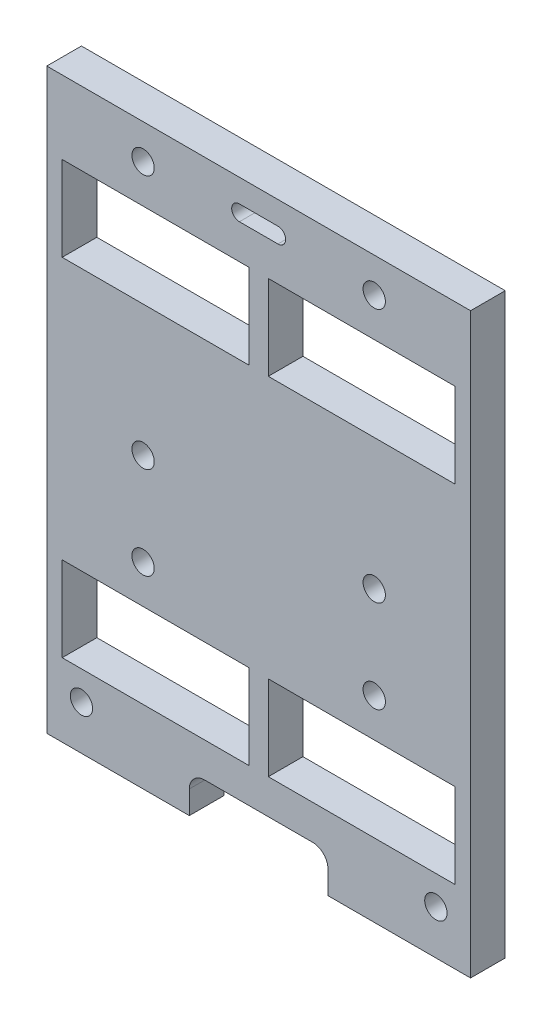
SolidWorks part; units mm, degrees
ref_plane "Front Plane" through (0, 0, 0) normal (0, 0, 1) x (1, 0, 0)
ref_plane "Top Plane" through (0, 0, 0) normal (0, 1, 0) x (1, 0, 0)
ref_plane "Right Plane" through (0, 0, 0) normal (1, 0, 0) x (0, 0, -1)
sketch "Sketch1" plane through (0, 0, 0) normal (0, 0, 1) x (1, 0, 0)
  line L0 (0, -37.5) -> (0, 37.5) construction
  line L1 (-27.5, -37.5) -> (27.5, -37.5)
  line L2 (-27.5, -37.5) -> (-27.5, 37.5)
  line L3 (-27.5, 37.5) -> (27.5, 37.5)
  line L4 (27.5, -37.5) -> (27.5, 37.5)
  line L5 (-27.5, -37.5) -> (27.5, 37.5) construction
  line L6 (-27.5, 37.5) -> (27.5, -37.5) construction
  line L7 (-27.5, 0) -> (27.5, 0) construction
  line L8 (-27.5, 22.5) -> (27.5, 22.5) construction
  line L9 (25.5, 17) -> (1.25, 28) construction
  line L10 (-25.5, 28) -> (-1.25, 28)
  line L11 (-25.5, 28) -> (-25.5, 17)
  line L12 (-25.5, 17) -> (-1.25, 17)
  line L13 (-1.25, 28) -> (-1.25, 17)
  line L14 (-25.5, 28) -> (-1.25, 17) construction
  line L15 (-25.5, 17) -> (-1.25, 28) construction
  line L16 (25.5, 28) -> (1.25, 17) construction
  line L17 (1.25, 28) -> (1.25, 17)
  line L18 (25.5, 17) -> (1.25, 17)
  line L19 (25.5, 28) -> (25.5, 17)
  line L20 (25.5, 28) -> (1.25, 28)
  line L21 (25.5, -28) -> (1.25, -17) construction
  line L22 (-25.5, -17) -> (-1.25, -28) construction
  line L23 (-25.5, -28) -> (-1.25, -17) construction
  line L24 (25.5, -17) -> (1.25, -28) construction
  line L25 (25.5, -28) -> (1.25, -28)
  line L26 (25.5, -28) -> (25.5, -17)
  line L27 (25.5, -17) -> (1.25, -17)
  line L28 (1.25, -28) -> (1.25, -17)
  line L29 (-1.25, -28) -> (-1.25, -17)
  line L30 (-25.5, -17) -> (-1.25, -17)
  line L31 (-25.5, -28) -> (-25.5, -17)
  line L32 (-25.5, -28) -> (-1.25, -28)
  point P0 (0, 0)
  point P12 (-13.375, 22.5)
  point P21 (13.375, 22.5)
  point P30 (13.375, -22.5)
  point P31 (-13.375, -22.5)
  dimension "D1" = 55
  dimension "D2" = 75
  dimension "D3" = 22.5
  dimension "D4" = 24.25
  dimension "D5" = 11
  dimension "D6" = 1.25
extrude "Boss-Extrude1" add sketch "Sketch1" along normal blind 4.5
sketch "Sketch2" plane through (0, 0, 4.5) normal (0, 0, 1) x (1, 0, 0)
  line L0 (0, -37.5) -> (0, 37.5) construction
  line L1 (-27.5, -37.5) -> (27.5, -37.5) construction
  line L2 (27.5, 37.5) -> (-27.5, 37.5) construction
  line L3 (-27.5, 0) -> (27.5, 0) construction
  line L4 (-27.5, 37.5) -> (-27.5, -37.5) construction
  line L5 (27.5, -37.5) -> (27.5, 37.5) construction
  line L6 (-15, 0) -> (15, 0) construction
  circle A0 centre (-15, 33) radius 1.45
  circle A1 centre (15, 33) radius 1.45
  circle A2 centre (15, 0) radius 1.45
  circle A3 centre (-15, 0) radius 1.45
  dimension "D1" = 2.9
  dimension "D7" = 2.9
  dimension "D8" = 2.9
  dimension "D2" = 15
  dimension "D3" = 33
  dimension "D4" = 30
  dimension "D5" = 15
  dimension "D6" = 0
extrude "screwHoles" cut sketch "Sketch2" against normal through all
sketch "Sketch3" plane through (0, 0, 4.5) normal (0, 0, 1) x (1, 0, 0)
  line L0 (-27.5, 9) -> (26.0486, 9) construction
  line L1 (-27.5, 37.5) -> (-27.5, -37.5) construction
  line L3 (0, 37.5) -> (0, -37.5) construction
  line L4 (27.5, 37.5) -> (-27.5, 37.5) construction
  line L5 (-27.5, -37.5) -> (27.5, -37.5) construction
  line L6 (18.95, 6.8) -> (9.05, 11.2) construction
  line L7 (-18.95, 11.2) -> (-9.05, 11.2)
  line L8 (-18.95, 11.2) -> (-18.95, 6.8)
  line L9 (-18.95, 6.8) -> (-9.05, 6.8)
  line L10 (-9.05, 11.2) -> (-9.05, 6.8)
  line L11 (-18.95, 11.2) -> (-9.05, 6.8) construction
  line L12 (-18.95, 6.8) -> (-9.05, 11.2) construction
  line L13 (18.95, 11.2) -> (9.05, 6.8) construction
  line L14 (9.05, 11.2) -> (9.05, 6.8)
  line L15 (18.95, 6.8) -> (9.05, 6.8)
  line L16 (18.95, 11.2) -> (18.95, 6.8)
  line L17 (18.95, 11.2) -> (9.05, 11.2)
  line L18 (-27.5, 37.5) -> (-27.5, -37.5) construction
  point P2 (-27.5, 0)
  point P12 (-14, 9)
  point P21 (14, 9)
  dimension "D1" = 9.9
  dimension "D2" = 4.4
  dimension "D3" = 14
  dimension "D4" = 9
extrude "BeltClamp" [suppressed] cut sketch "Sketch3" against normal through all
sketch "Sketch4" plane through (0, 0, 4.5) normal (0, 0, 1) x (1, 0, 0)
  line L0 (-27.5, 0) -> (27.5, 0) construction
  line L1 (-27.5, 37.5) -> (-27.5, -37.5) construction
  line L2 (27.5, -37.5) -> (27.5, 37.5) construction
  line L4 (-4.9, 2.2) -> (4.9, 2.2)
  line L5 (-4.9, 2.2) -> (-4.9, -2.2)
  line L6 (-4.9, -2.2) -> (4.9, -2.2)
  line L7 (4.9, 2.2) -> (4.9, -2.2)
  line L8 (-4.9, 2.2) -> (4.9, -2.2) construction
  line L9 (-4.9, -2.2) -> (4.9, 2.2) construction
  circle A0 centre (-15, 0) radius 1.45 construction
  point P6 (0, 0)
  dimension "D2" = 4.4
  dimension "D3" = 0
extrude "mountingPlateTab" [suppressed] cut sketch "Sketch4" against normal through all
sketch "Sketch5" plane through (0, 0, 4.5) normal (0, 0, 1) x (1, 0, 0)
  line L0 (-27.5, -9.75) -> (27.5, -9.75) construction
  line L1 (-27.5, 37.5) -> (-27.5, -37.5) construction
  line L2 (27.5, -37.5) -> (27.5, 37.5) construction
  line L4 (0, -37.5) -> (0, 37.5) construction
  line L5 (-27.5, -37.5) -> (27.5, -37.5) construction
  line L6 (27.5, 37.5) -> (-27.5, 37.5) construction
  line L7 (-20.8, -14.65) -> (-25.2, -4.85) construction
  line L8 (20.8, -4.85) -> (25.2, -4.85)
  line L9 (20.8, -4.85) -> (20.8, -14.65)
  line L10 (20.8, -14.65) -> (25.2, -14.65)
  line L11 (25.2, -4.85) -> (25.2, -14.65)
  line L12 (20.8, -4.85) -> (25.2, -14.65) construction
  line L13 (20.8, -14.65) -> (25.2, -4.85) construction
  line L14 (-20.8, -4.85) -> (-25.2, -14.65) construction
  line L15 (-25.2, -4.85) -> (-25.2, -14.65)
  line L16 (-20.8, -14.65) -> (-25.2, -14.65)
  line L17 (-20.8, -4.85) -> (-20.8, -14.65)
  line L18 (-20.8, -4.85) -> (-25.2, -4.85)
  line L19 (23, -9.75) -> (23, -37.5) construction
  line L20 (-23, -9.75) -> (-23, -37.5) construction
  circle A0 centre (23, -31.75) radius 1.45
  circle A1 centre (-23, -31.75) radius 1.45
  point P15 (23, -9.75)
  point P24 (-23, -9.75)
  dimension "D5" = 2.9
  dimension "D2" = 9.8
  dimension "D3" = 4.4
  dimension "D4" = 23
  dimension "D6" = 22
  dimension "D1" = 9.75
extrude "BraceTabs" cut sketch "Sketch5" against normal through all
sketch "Sketch6" [suppressed] plane through (0, 0, 4.5) normal (0, 0, 1) x (1, 0, 0)
  line L0 (-25.2, -9.75) -> (25.2, -9.75) construction
  line L1 (-25.2, -4.85) -> (-25.2, -14.65) construction
  line L2 (25.2, -14.65) -> (25.2, -4.85) construction
  line L3 (0, -2.2) -> (0, -37.5) construction
  line L4 (-4.9, -2.2) -> (4.9, -2.2) construction
  line L5 (-27.5, -37.5) -> (27.5, -37.5) construction
  line L6 (23, -14.65) -> (23, -4.85) construction
  line L7 (20.8, -14.65) -> (25.2, -14.65) construction
  line L8 (25.2, -4.85) -> (20.8, -4.85) construction
  line L9 (20.8, -4.85) -> (20.8, -14.65) construction
  line L10 (19.8, -15.65) -> (26.2, -15.65)
  line L11 (19.8, -15.65) -> (19.8, -3.85)
  line L12 (19.8, -3.85) -> (26.2, -3.85)
  line L13 (26.2, -15.65) -> (26.2, -3.85)
  line L14 (19.8, -15.65) -> (26.2, -3.85) construction
  line L15 (19.8, -3.85) -> (26.2, -15.65) construction
  line L16 (-19.8, -3.85) -> (-26.2, -15.65) construction
  line L17 (-19.8, -15.65) -> (-26.2, -3.85) construction
  line L18 (-23, -14.65) -> (-23, -4.85) construction
  line L19 (-26.2, -15.65) -> (-26.2, -3.85)
  line L20 (-19.8, -3.85) -> (-26.2, -3.85)
  line L21 (-19.8, -15.65) -> (-19.8, -3.85)
  line L22 (-19.8, -15.65) -> (-26.2, -15.65)
  circle A0 centre (23, -9.75) radius 1.45
  circle A1 centre (-23, -9.75) radius 1.45
  point P18 (23, -9.75)
  dimension "D3" = 2.9
  dimension "D1" = 1
  dimension "D2" = 1
extrude "FrontToRear1" [suppressed] add sketch "Sketch6" against normal up to surface (4.5 mm away) up to face at (-24.45, -31.75, 0)
sketch "Sketch7" [suppressed] plane through (0, 0, 4.5) normal (0, 0, 1) x (1, 0, 0)
  line L0 (4.9, 2.2) -> (-4.9, 2.2) construction
  line L1 (-20, -3.2) -> (20, -3.2)
  line L2 (-20, -3.2) -> (-20, 3.2)
  line L3 (-20, 3.2) -> (20, 3.2)
  line L4 (20, -3.2) -> (20, 3.2)
  line L5 (-20, -3.2) -> (20, 3.2) construction
  line L6 (-20, 3.2) -> (20, -3.2) construction
  circle A0 centre (15, 0) radius 1.45 construction
  point P0 (0, 0)
  dimension "D1" = 1
  dimension "D2" = 5
extrude "FrontToRear2" [suppressed] add sketch "Sketch7" against normal through all
sketch "Sketch8" plane through (0, 0, 4.5) normal (0, 0, 1) x (1, 0, 0)
  line L0 (-27.5, -12) -> (27.5, -12) construction
  line L1 (-27.5, 37.5) -> (-27.5, -37.5) construction
  line L2 (27.5, -37.5) -> (27.5, 37.5) construction
  line L3 (0, -37.5) -> (0, 0) construction
  line L4 (-27.5, -37.5) -> (27.5, -37.5) construction
  circle A0 centre (-15, -12) radius 1.45
  circle A1 centre (15, -12) radius 1.45
  dimension "D2" = 2.9
  dimension "D1" = 12
  dimension "D3" = 15
extrude "ExpansionScrewholes" cut sketch "Sketch8" against normal through all
sketch "Sketch12" plane through (0, 0, 4.5) normal (0, 0, 1) x (1, 0, 0)
  line L0 (0, 37.5) -> (0, 0) construction
  line L1 (27.5, 37.5) -> (-27.5, 37.5) construction
  line L2 (-2.5, 33.5) -> (2.5, 33.5) construction
  line L3 (-2.5, 34.5) -> (2.5, 34.5)
  line L4 (-2.5, 32.5) -> (2.5, 32.5)
  arc A0 (-2.5, 34.5) -> (-2.5, 32.5) centre (-2.5, 33.5) ccw
  arc A1 (2.5, 32.5) -> (2.5, 34.5) centre (2.5, 33.5) ccw
  point P7 (0, 33.5)
  dimension "D1" = 3
  dimension "D2" = 2
  dimension "D3" = 5
extrude "CableTieSlot" cut sketch "Sketch12" against normal through all
sketch "Sketch11" plane through (0, 0, 4.5) normal (0, 0, 1) x (1, 0, 0)
  line L0 (13.5615, -8.65) -> (27.5, -8.65) construction
  line L1 (27.5, -37.5) -> (27.5, 37.5) construction
  line L2 (0, 37.5) -> (0, -37.5) construction
  line L3 (36.5, -14.65) -> (18.5, -14.65)
  line L4 (36.5, -14.65) -> (36.5, -2.65)
  line L5 (36.5, -2.65) -> (18.5, -2.65)
  line L6 (18.5, -14.65) -> (18.5, -2.65)
  line L7 (36.5, -14.65) -> (18.5, -2.65) construction
  line L8 (36.5, -2.65) -> (18.5, -14.65) construction
  line L11 (-36.5, -2.65) -> (-18.5, -14.65) construction
  line L12 (-36.5, -14.65) -> (-18.5, -2.65) construction
  line L13 (-18.5, -14.65) -> (-18.5, -2.65)
  line L14 (-36.5, -2.65) -> (-18.5, -2.65)
  line L15 (-36.5, -14.65) -> (-36.5, -2.65)
  line L16 (-36.5, -14.65) -> (-18.5, -14.65)
  line L17 (36.5, -2.65) -> (18.5, -14.65) construction
  line L18 (20.8, -14.65) -> (25.2, -14.65) construction
  line L19 (27.5, 37.5) -> (-27.5, 37.5) construction
  line L20 (-27.5, -37.5) -> (27.5, -37.5) construction
  dimension "D1" = 9
  dimension "D2" = 12
  dimension "D3" = 0
extrude "Cut-Extrude2" [suppressed] cut sketch "Sketch11" against normal through all
sketch "Sketch10" [suppressed] plane through (0, 0, 4.5) normal (0, 0, 1) x (1, 0, 0)
  line L0 (4.7446, 1) -> (27.5, 1) construction
  line L1 (-4.9, 0) -> (4.9, 0) construction
  line L2 (27.5, -37.5) -> (27.5, 37.5) construction
  line L3 (0, 2.2) -> (0, -2.2) construction
  line L4 (36.5, 4) -> (18.5, 4)
  line L5 (36.5, 4) -> (36.5, -2)
  line L6 (36.5, -2) -> (18.5, -2)
  line L7 (18.5, 4) -> (18.5, -2)
  line L8 (36.5, 4) -> (18.5, -2) construction
  line L9 (36.5, -2) -> (18.5, 4) construction
  line L10 (4.9, 2.2) -> (-4.9, 2.2) construction
  line L11 (-4.9, -2.2) -> (4.9, -2.2) construction
  line L12 (-36.5, -2) -> (-18.5, 4) construction
  line L13 (-36.5, 4) -> (-18.5, -2) construction
  line L14 (-4.7446, 1) -> (-27.5, 1) construction
  line L15 (-18.5, 4) -> (-18.5, -2)
  line L16 (-36.5, -2) -> (-18.5, -2)
  line L17 (-36.5, 4) -> (-36.5, -2)
  line L18 (-36.5, 4) -> (-18.5, 4)
  line L19 (36.5, -2) -> (18.5, 4) construction
  line L20 (-4.9, 2.2) -> (-4.9, -2.2) construction
  line L21 (4.9, -2.2) -> (4.9, 2.2) construction
  dimension "D1" = 6
  dimension "D2" = 9
  dimension "D3" = 1
extrude "CableTieSlots" [suppressed] cut sketch "Sketch10" against normal through all
sketch "Sketch9" plane through (0, 0, 4.5) normal (0, 0, 1) x (1, 0, 0)
  line L0 (-27.5, -37.5) -> (27.5, -37.5) construction
  line L5 (-9, -42.5) -> (9, -42.5)
  line L6 (-9, -42.5) -> (-9, -34.5)
  line L7 (-7, -32.5) -> (7, -32.5)
  line L8 (9, -42.5) -> (9, -34.5)
  line L9 (-9, -42.5) -> (9, -32.5) construction
  line L10 (-9, -32.5) -> (9, -42.5) construction
  arc A0 (7, -32.5) -> (9, -34.5) centre (7, -34.5) cw
  arc A1 (-9, -34.5) -> (-7, -32.5) centre (-7, -34.5) cw
  point P9 (0, -37.5)
  line M42 (-27.5, -37.5) -> (27.5, -37.5)
  dimension "D3" = 2
  dimension "D1" = 18
  dimension "D2" = 5
extrude "RearFanSlot" cut sketch "Sketch9" against normal through all contours A1 L6 L8 A0 L7 M42 | L5 L8 L6 M42
sketch "Sketch13" [suppressed] plane through (0, 0, 4.5) normal (0, 0, 1) x (1, 0, 0)
  line L1 (-7, -2.85) -> (7, -2.85)
  line L2 (-7, -2.85) -> (-7, -11.85)
  line L3 (-7, -11.85) -> (7, -11.85)
  line L4 (7, -2.85) -> (7, -11.85)
  line L5 (-7, -2.85) -> (7, -11.85) construction
  line L6 (-7, -11.85) -> (7, -2.85) construction
  line L9 (0, 37.5) -> (0, -7.35) construction
  line L10 (-18.5, -2.85) -> (-27.5, -2.85) construction
  line L11 (27.5, 37.5) -> (-27.5, 37.5) construction
  line L13 (-27.5, -14.85) -> (-18.5, -14.85) construction
  point P0 (0, -7.35)
  dimension "D1" = 3
  dimension "D2" = 0
  dimension "D3" = 7
extrude "Cut-Extrude3" [suppressed] cut sketch "Sketch13" against normal through all
sketch "Sketch14" plane through (0, 0, 4.5) normal (0, 0, 1) x (1, 0, 0)
  line L0 (25.2, -4.85) -> (20.8, -4.85) construction
  line L1 (25.2, -4.85) -> (20.8, -4.85)
  line L2 (25.2, -4.85) -> (25.2, -14.65)
  line L3 (25.2, -14.65) -> (20.8, -14.65)
  line L4 (20.8, -4.85) -> (20.8, -14.65)
  line L5 (25.2, -14.65) -> (25.2, -4.85) construction
  line L6 (0, 0) -> (0, -6.835) construction
  line L7 (-20.8, -4.85) -> (-20.8, -14.65)
  line L8 (-25.2, -14.65) -> (-20.8, -14.65)
  line L9 (-25.2, -4.85) -> (-25.2, -14.65)
  line L10 (-25.2, -4.85) -> (-20.8, -4.85)
extrude "Boss-Extrude2" add sketch "Sketch14" against normal through all
equation "\"X-ROD-SPACING\"=45"
equation "\"Y-ROD-SPACING\"=75"
equation "\"Z-ROD-SPACING\"=17.5"
equation "\"Y-BED-OFFSET\"=2"
equation "\"Y-BED-ROD-INSET\"=3.5"
equation "\"Y-BED-SCREW-SPACING\"=209"
equation "\"Y-BED-SCREW-CUTOUT-SLOT-HEIGHT\"=2"
equation "\"T-SLOT-NUT-FILLET-RADIUS\"=0.5"
equation "\"T-SLOT-SCREW-SHAFT-RADIUS\"=1.55"
equation "\"T-SLOT-SCREW-SHAFT-CUTOUT-LENGTH\"=11.0"
equation "\"T-SLOT-NUT-DEPTH\"=3.5"
equation "\"T-SLOT-NUT-WIDTH\"=2.85"
equation "\"T-SLOT-NUT-END-DISTANCE\"=8"
equation "\"ACRYLIC-THICKNESS\"=10"
equation "\"ACRYLIC-THICKNESS2\"=4.5"
equation "\"ACRYLIC-TAB-CUTOUT-SIZE\"=\"ACRYLIC-THICKNESS\"+\"ACRYLIC-TAB-TOLERANCE\"*2"
equation "\"ACRYLIC-TAB-WIDTH\"=\"ACRYLIC-THICKNESS\""
equation "\"ACRYLIC-M3-HOLE\"=2.9"
equation "\"SMOOTHROD-CAP-SCREW-DISTANCE\"=20"
equation "\"FRAME-WIDTH-INNER\"=370"
equation "\"NEMA17-HOLE-SPACING\"=31"
equation "\"NEMA17-CENTRAL-CUTOUT\"=22.5"
equation "\"Z-BRACKET-REACH\"=55"
equation "\"Z-ROD-INSET\"=16"
equation "\"TOP-BRACKET-SPACING\"=40"
equation "\"SMOOTHROD-X-LENGTH\"=350"
equation "\"SMOOTHROD-Y-LENGTH\"=350"
equation "\"SMOOTHROD-Z-LENGTH\"=350"
equation "\"SMOOTHROD-TIGHTENING-HEADROOM\"=.25"
equation "\"LEADSCREW-Z-LENGTH\"=300"
equation "\"SCREW-LENGTH-FRAME\"=\"ACRYLIC-THICKNESS\" + 10"
equation "\"SCREW-LENGTH-MOTOR\"=\"ACRYLIC-THICKNESS\" + 5"
equation "\"SCREW-HEAD-RADIUS\"=6"
equation "\"PRINTED-X-SMOOTHROD-DIAMETER\"=8.4"
equation "\"PRINTED-X-SMOOTHROD-CUTOUT\"=10"
equation "\"PRINTED-X-BASE-HEIGHT\"=10"
equation "\"PRINTED-LM8UU-CUTOUT-SIZE\"=15.5"
equation "\"PRINTED-LM8UU-CUTOUT-LENGTH\"=24.5"
equation "\"PRINTED-X-IDLER-HEIGHT\"=16"
equation "\"PSU-MOUNTING-WIDTH\"=95"
equation "\"PSU-MOUNTING-HEIGHT\"=177"
equation "\"Y-BELT-TO-ROD-DISTANCE\"=20"
equation "\"SPOOL-HOLDER-ROD-SPACING\"=150"
equation "\"D3@Sketch1\"=\"X-ROD-SPACING\"/2"
equation "\"D4@Sketch1\"=\"ACRYLIC-X-CARRIAGE-LM8UU-CUTOUT-WIDTH\""
equation "\"D1@Boss-Extrude1\"=\"ACRYLIC-THICKNESS2\""
equation "\"D1@Sketch2\"=\"ACRYLIC-M3-HOLE\""
equation "\"D1@Sketch3\"=\"ACRYLIC-TAB-CUTOUT-SIZE\""
equation "\"D2@Sketch3\"=\"ACRYLIC-THICKNESS2\"+\"ACRYLIC-TAB-TOLERANCE\"*2"
equation "\"ACRYLIC-X-CARRIAGE-WIDTH\"=55"
equation "\"ACRYLIC-X-CARRIAGE-HEIGHT\"=75"
equation "\"D1@Sketch1\"=\"ACRYLIC-X-CARRIAGE-WIDTH\""
equation "\"D2@Sketch1\"=\"ACRYLIC-X-CARRIAGE-HEIGHT\""
equation "\"ACRYLIC-X-CARRIAGE-CENTER-TAB-SPACING\"=14"
equation "\"D3@Sketch3\"=\"ACRYLIC-X-CARRIAGE-CENTER-TAB-SPACING\""
equation "\"SCREW-LENGTH-EXTRUDER\"=28"
equation "\"ACRYLIC-X-CARRIAGE-SCREW-SPACING-X\"=15"
equation "\"ACRYLIC-X-CARRIAGE-SCREW-SPACING-Y\"=33"
equation "\"D2@Sketch2\"=\"ACRYLIC-X-CARRIAGE-SCREW-SPACING-X\""
equation "\"D3@Sketch2\"=\"ACRYLIC-X-CARRIAGE-SCREW-SPACING-Y\""
equation "\"D1@Sketch4\"=\"ACRYLIC-TAB-WIDTH\"-\"KERF\"*4"
equation "\"D2@Sketch4\"=\"ACRYLIC-THICKNESS2\"-\"KERF\"*2"
equation "\"D2@Sketch5\"=\"ACRYLIC-TAB-WIDTH\"-\"KERF\"*4"
equation "\"D3@Sketch5\"=\"ACRYLIC-THICKNESS2\"-\"KERF\"*2"
equation "\"ACRYLIC-X-CARRIAGE-EXTRUDER-SHELF-DEPTH\"=\"ACRYLIC-X-CARRIAGE-EXTRUDER-OFFSET\" + 28"
equation "\"ACRYLIC-X-CARRIAGE-EXTRUDER-BRACE-SPACING\"=23"
equation "\"D4@Sketch5\"=\"ACRYLIC-X-CARRIAGE-EXTRUDER-BRACE-SPACING\""
equation "\"D4@Sketch2\"=\"ACRYLIC-X-CARRIAGE-SCREW-SPACING-X\"*2"
equation "\"D5@Sketch2\"=\"ACRYLIC-X-CARRIAGE-SCREW-SPACING-X\""
equation "\"D7@Sketch2\"=\"ACRYLIC-M3-HOLE\""
equation "\"D8@Sketch2\"=\"ACRYLIC-M3-HOLE\""
equation "\"ACRYLIC-X-CARRIAGE-LM8UU-CUTOUT-WIDTH\"=24.25"
equation "\"ACRYLIC-TAB-TOLERANCE\"=-.05"
equation "\"ACRYLIC-X-CARRIAGE-EXTRUDER-OFFSET\"=26"
equation "\"ACRYLIC-X-CARRIAGE-EXTRUDER-ANGLE\"=90"
equation "\"ACRYLIC-X-CARRIAGE-EXTRUDER-BRACE-TAB-OFFSET\"=20"
equation "\"ACRYLIC-X-CARRIAGE-EXTRUDER-BRACE-HEIGHT\"=35"
equation "\"ACRYLIC-X-CARRIAGE-EXTRUDER-BRACE-SCREW-SPACING\"=22"
equation "\"D5@Sketch5\"=\"ACRYLIC-M3-HOLE\""
equation "\"D3@Sketch6\"=\"ACRYLIC-M3-HOLE\""
equation "\"ACRYLIC-X-CARRIAGE-LM8UU-CUTOUT-HEIGHT\"=11.0"
equation "\"ACRYLIC-X-CARRIAGE-DUAL-WIDTH-MULTIPLIER\"=1.65"
equation "\"ACRYLIC-X-CARRIAGE-DUAL-HOTEND-SPACING\"=42"
equation "\"ACRYLIC-X-CARRIAGE-DUAL-WIDTH\"=75"
equation "\"ACRYLIC-X-CARRIAGE-DUAL-HOTEND-SEPARATION\"=36"
equation "\"ACRYLIC-X-CARRIAGE-DUAL-MOUNT-PLATE-DEPTH\"=75"
equation "\"ACRYLIC-X-CARRIAGE-DUAL-MOUNT-BRACE-WIDTH\"=33"
equation "\"ACRYLIC-X-CARRIAGE-DUAL-MOUNT-SCREW-WIDTH\"=40"
equation "\"D5@Sketch1\"=\"ACRYLIC-X-CARRIAGE-LM8UU-CUTOUT-HEIGHT\""
equation "\"D2@Sketch8\"=\"ACRYLIC-M3-HOLE\""
equation "\"D1@Sketch5\"=\"ACRYLIC-THICKNESS2\"/2 + 7.5"
equation "\"KERF\"=0.05"
equation "\"PRINTED-M3-HOLE\"=3.5"
equation "\"PRINTED-M3-NUT-AF\"=6.25"
equation "\"ACRYLIC-X-CARRIAGE-DUAL-FAN-OFFSET\"=52"
equation "\"ACRYLIC-X-CARRIAGE-DUAL-FAN-HEIGHT\"=20"
equation "\"BLOWER-FAN-WIDTH\"=15"
